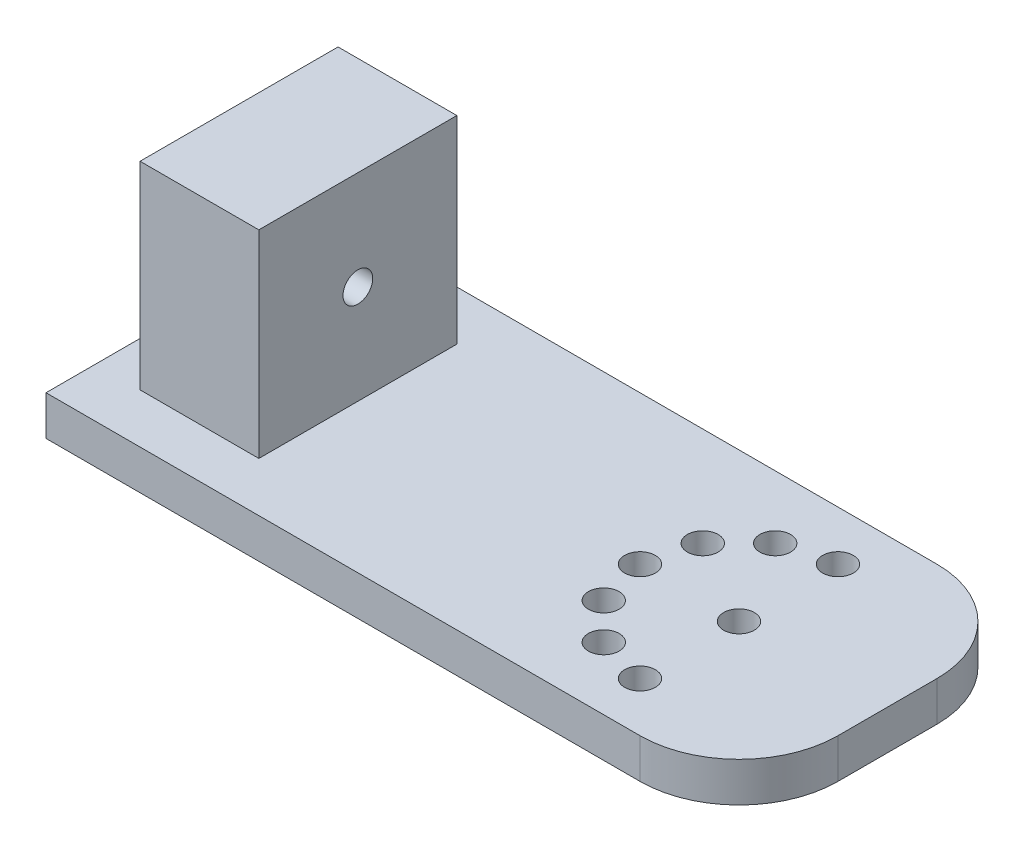
SolidWorks part; units mm, degrees
ref_plane "前视基准面" through (0, 0, 0) normal (0, 0, 1) x (1, 0, 0)
ref_plane "上视基准面" through (0, 0, 0) normal (0, 1, 0) x (1, 0, 0)
ref_plane "右视基准面" through (0, 0, 0) normal (1, 0, 0) x (0, 0, -1)
sketch "草图1" plane through (0, 0, 0) normal (0, 1, 0) x (1, 0, 0)
  line L1 (0, 0) -> (70, 0)
  line L2 (0, 0) -> (0, -30)
  line L3 (0, -30) -> (70, -30)
  line L4 (70, 0) -> (70, -30)
extrude "凸台-拉伸1" add sketch "草图1" along normal blind 4
sketch "草图2" plane through (0, 4, 0) normal (0, 1, 0) x (1, 0, 0)
  line L0 (70, 0) -> (0, 0) construction
  line L1 (4.5, -5) -> (16.5, -5)
  line L2 (4.5, -5) -> (4.5, -25)
  line L3 (4.5, -25) -> (16.5, -25)
  line L4 (16.5, -5) -> (16.5, -25)
  line L5 (0, 0) -> (0, -30) construction
  dimension "D1" = 5
  dimension "D2" = 4.5
extrude "凸台-拉伸2" add sketch "草图2" along normal blind 20
sketch "草图7" plane through (16.5, 0, 0) normal (1, 0, 0) x (0, 0, -1)
  line L0 (-25, 24) -> (-25, 4) construction
  line L1 (-25, 4) -> (-5, 4) construction
  circle A0 centre (-15, 14) radius 1.5
  dimension "D1" = 10
  dimension "D2" = 10
extrude "切除-拉伸2" cut sketch "草图7" against normal blind 12
sketch "草图11" plane through (0, 4, 0) normal (0, 1, 0) x (1, 0, 0)
  line L0 (70, -30) -> (70, 0) construction
  line L1 (0, -30) -> (70, -30) construction
  line L2 (55, -5) -> (55, -15) construction
  line L3 (55, -15) -> (60, -6.3397) construction
  line L4 (55, -15) -> (63.6603, -10) construction
  line L5 (60, -23.6603) -> (55, -15) construction
  line L6 (55, -15) -> (63.6603, -20) construction
  line L7 (65, -15) -> (45, -15) construction
  line L8 (55, -15) -> (55, -25) construction
  line L10 (55, -15) -> (46.3397, -20) construction
  line L11 (50, -23.6603) -> (55, -15) construction
  line L12 (55, -15) -> (46.3397, -10) construction
  line L13 (55, -15) -> (50, -6.3397) construction
  circle A0 centre (55, -15) radius 1.55
  circle A1 centre (55, -15) radius 10 construction
  circle A9 centre (50, -23.6603) radius 1.55
  circle A10 centre (46.3397, -20) radius 1.55
  circle A11 centre (46.3397, -10) radius 1.55
  circle A12 centre (50, -6.3397) radius 1.55
  circle A13 centre (45, -15) radius 1.55
  circle A14 centre (55, -5) radius 1.55
  circle A15 centre (55, -25) radius 1.55
  dimension "D1" = 15
  dimension "D3" = 30
  dimension "D8" = 30
  dimension "D4" = 3.1
  dimension "D5" = 30
  dimension "D6" = 20
  dimension "D2" = 15
  dimension "D7" = 30
  dimension "D9" = 30
extrude "切除-拉伸4" cut sketch "草图11" against normal blind 50
fillet "圆角1" radius 10 1 edges at (70, 2, 30) type face fillet first side face at (35, 2, 30) second side face at (70, 2, 15)
fillet "圆角2" radius 10 1 edges at (70, 2, 0) type face fillet first side face at (35, 2, 0) second side face at (70, 2, 10)
